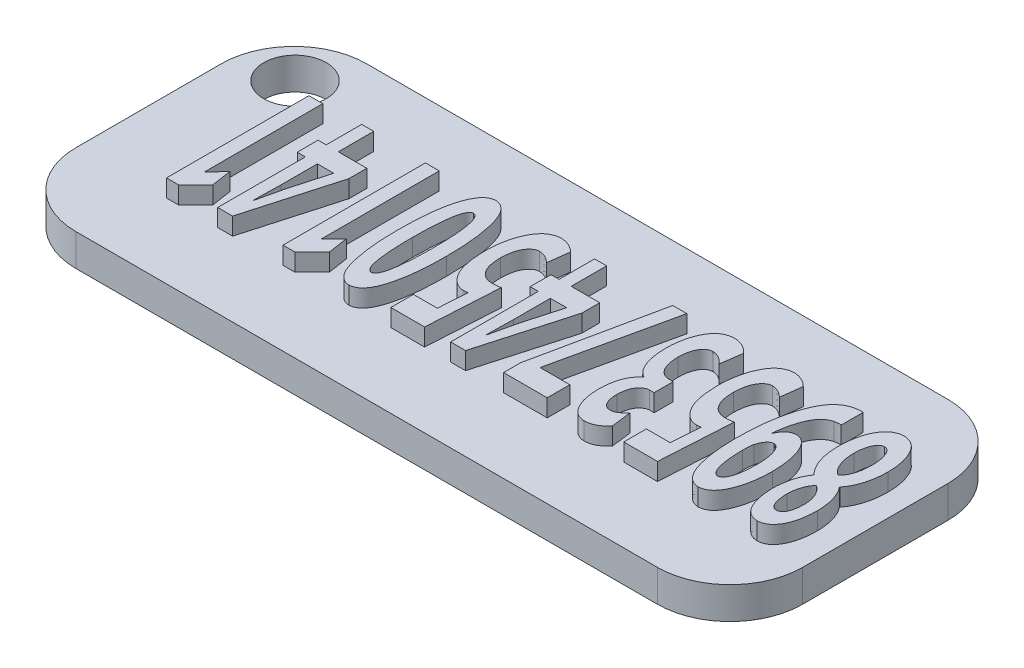
SolidWorks part; units mm, degrees
ref_plane "Спереди" through (0, 0, 0) normal (0, 0, 1) x (1, 0, 0)
ref_plane "Сверху" through (0, 0, 0) normal (0, 1, 0) x (1, 0, 0)
ref_plane "Справа" through (0, 0, 0) normal (1, 0, 0) x (0, 0, -1)
other "Configuration Table"
sketch "Эскиз1" plane through (0, 0, 0) normal (0, 1, 0) x (1, 0, 0)
  line L1 (0, 0) -> (50, 0)
  line L2 (0, 0) -> (0, 20)
  line L3 (0, 20) -> (50, 20)
  line L4 (50, 0) -> (50, 20)
  dimension "D1" = 20
  dimension "D2" = 50
extrude "Бобышка-Вытянуть1" add sketch "Эскиз1" along normal blind 2.2 contours L2 L3 L4 L1
fillet "Скругление1" radius 5 1 edges at (0, 1.1, -20)
fillet "Скругление2" radius 5 1 edges at (0, 1.1, 0)
fillet "Скругление3" radius 5 1 edges at (50, 1.1, -20)
fillet "Скругление4" radius 5 1 edges at (50, 1.1, 0)
sketch "Эскиз4" plane through (0, 2.2, 0) normal (0, 1, 0) x (1, 0, 0)
  circle A0 centre (3.5425, 16.5284) radius 2.1519
extrude "Вырез-Вытянуть1" cut sketch "Эскиз4" against normal blind 3
sketch "Эскиз5" plane through (0, 2.2, 0) normal (0, -1, 0) x (1, 0, 0)
  line L0 (0, -15) -> (50.4167, -15) construction
  arc A0 (0, -15) -> (5, -20) centre (5, -15) ccw construction
  text T0 "<b> 89537450141</b>" font "@Adobe Gothic Std B" height 10
extrude "надпись" add sketch "Эскиз5" along normal blind 1.2 and the other way blind 1.2
